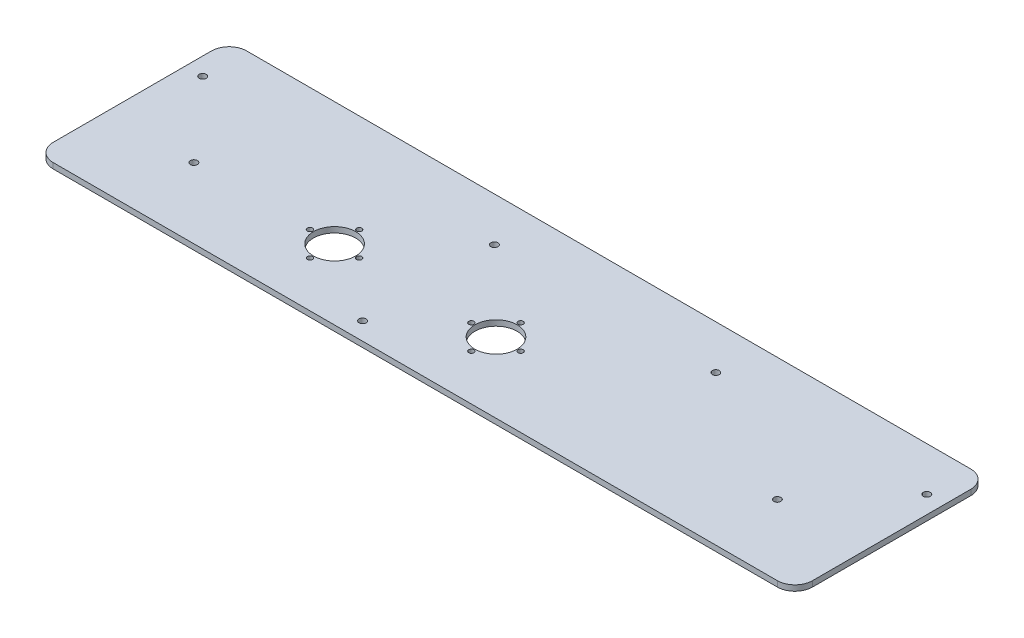
SolidWorks part; units mm, degrees
ref_plane "Front" through (0, 0, 0) normal (0, 0, 1) x (1, 0, 0)
ref_plane "Top" through (0, 0, 0) normal (0, 1, 0) x (1, 0, 0)
ref_plane "Right" through (0, 0, 0) normal (1, 0, 0) x (0, 0, -1)
sketch "Sketch1" plane through (0, 0, 0) normal (0, 1, 0) x (1, 0, 0)
  line L0 (-26.7996, 0) -> (-26.7996, 40)
  line L1 (-26.7996, 0) -> (405.0004, 0)
  line L2 (-26.7996, 0) -> (-26.7996, 110)
  line L3 (-26.7996, 110) -> (405.0004, 110)
  line L4 (405.0004, 0) -> (405.0004, 110)
  line L5 (-26.7996, 40) -> (23.2004, 40)
  line L6 (405.0004, 0) -> (405.0004, 40)
  line L7 (405.0004, 40) -> (355.0004, 40)
  line L8 (23.2004, 40) -> (103.2004, 40)
  line L9 (355.0004, 40) -> (195.0004, 40)
  line L10 (-26.7996, 110) -> (-26.7996, 85)
  line L11 (-26.7996, 85) -> (405.0004, 85)
  line L12 (-26.7996, 85) -> (-16.7996, 85)
  line L13 (405.0004, 85) -> (395.0004, 85)
  line L14 (103.2004, 40) -> (195.0004, 40)
  line L15 (149.1004, 40) -> (149.1004, 85)
  line L16 (275.0004, 40) -> (275.0004, 85)
  line L17 (149.1004, 40) -> (149.1004, 10)
  circle A10 centre (355.0004, 40) radius 2
  circle A11 centre (23.2004, 40) radius 2
  circle A12 centre (103.2004, 40) radius 12
  circle A13 centre (103.2004, 40) radius 14
  circle A15 centre (103.2004, 54) radius 1.5
  circle A16 centre (89.2004, 40) radius 1.5
  circle A17 centre (103.2004, 26) radius 1.5
  circle A18 centre (117.2004, 40) radius 1.5
  circle A19 centre (195.0004, 40) radius 12
  circle A20 centre (195.0004, 40) radius 14
  circle A21 centre (195.0004, 26) radius 1.5
  circle A22 centre (209.0004, 40) radius 1.5
  circle A23 centre (195.0004, 54) radius 1.5
  circle A24 centre (181.0004, 40) radius 1.5
  circle A25 centre (-16.7996, 85) radius 2
  circle A26 centre (395.0004, 85) radius 2
  circle A27 centre (149.1004, 85) radius 2
  circle A28 centre (275.0004, 85) radius 2
  circle A29 centre (149.1004, 10) radius 2
  dimension "D3" = 40
  dimension "D7" = 80
  dimension "D8" = 160
  dimension "D9" = 25
  dimension "D11" = 10
  dimension "D12" = 30
  dimension "D1" = 110
  dimension "D2" = 431.8
  dimension "D4" = 50
  dimension "D5" = 40
  dimension "D6" = 50
  dimension "D10" = 10
extrude "Boss-Extrude1" add sketch "Sketch1" along normal blind 3.175 contours A18 L14 A12 L8 A16 A13 A17 | A18 A13 A15 A16 L8 A12 L14 | A24 L14 A19 L9 A22 A20 A23 | A24 A20 A21 A22 L9 A19 L14 | A29 L14 A18 A13 A17 A16 L8 A11 L5 L0 L1 L4 L7 A10 L9 A22 A20 A21 A24 | A28 L11 A27 L15 L14 A24 A20 A23 A22 L9 L16 | A27 L11 A25 L2 L5 A11 L8 A16 A13 A15 A18 L14 L15 | A28 L11 A26 L13 L4 L3 L2 A25 A27 | A28 L16 L9 A10 L7 L4 L13 A26 L11 region at (190.6477, 0, -19.4614) region at (59.4634, 0, -63.1773) region at (189.0736, 0, -97.5272) region at (339.9596, 0, -62.4883) region at (93.521, 0, -49.6794) region at (90.515, 0, -38.754) region at (213.0557, 0, -63.4486) region at (207.6858, 0, -41.246) region at (204.6798, 0, -30.3206)
fillet "Fillet1" radius 10 4 edges at (405.0004, 1.5875, -110) (405.0004, 1.5875, 0) (-26.7996, 1.5875, 0) (-26.7996, 1.5875, -110)
